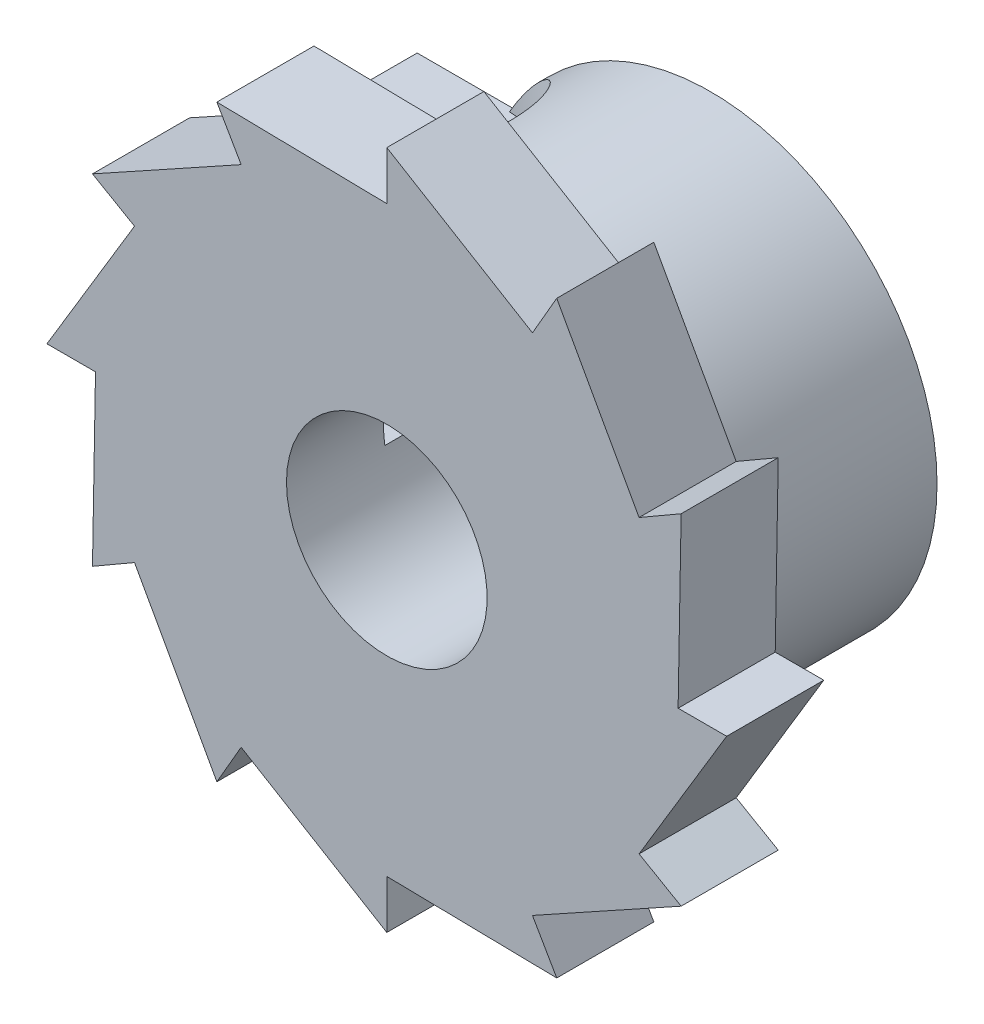
SolidWorks part; units mm, degrees
ref_plane "Front Plane" through (0, 0, 0) normal (0, 0, 1) x (1, 0, 0)
ref_plane "Top Plane" through (0, 0, 0) normal (0, 1, 0) x (1, 0, 0)
ref_plane "Right Plane" through (0, 0, 0) normal (1, 0, 0) x (0, 0, -1)
sketch "Sketch1" plane through (0, 0, 0) normal (0, 0, 1) x (1, 0, 0)
  line L0 (0, 9) -> (0, 10.5)
  line L1 (0.0027, 10.5) -> (-49999.9973, 10.5) construction
  line L2 (0, 0) -> (0, 50000) construction
  line L3 (-0.0178, -0.0309) -> (24999.9822, 43301.2393) construction
  line L4 (0, 9) -> (0, 3.1)
  line L5 (4.5, 7.7942) -> (1.55, 2.6847)
  line L6 (4.5, 7.7942) -> (0, 10.5)
  circle A0 centre (0, 0) radius 9 construction
  circle A1 centre (0, 0) radius 3.1 construction
  arc A2 (0, 10.5) -> (4.5, 7.7942) centre (0, 5.4051) cw construction
  arc A3 (0, 3.1) -> (1.55, 2.6847) centre (0, 0) cw
  dimension "D1" = 6.2
  dimension "D2" = 18
  dimension "D3" = 30
  dimension "D4" = 1.5
extrude "Boss-Extrude1" add sketch "Sketch1" along normal blind 3
pattern_circular "CirPattern1" count 12 over 360 about axis through (0, 0, 3) along (0, 0, -1) of "Boss-Extrude1"
sketch "Sketch3" plane through (0, 0, 0) normal (0, 0, -1) x (-1, 0, 0)
  line L0 (7, -3.5) -> (7, -7)
  line L2 (-7, 0) -> (-7, 7)
  line L3 (-7, 7) -> (9.0622, 7)
  line L5 (7, -7) -> (0, -7)
  line L7 (9.0622, 3.5) -> (9.0622, -3.5)
  line L8 (9.0622, -3.5) -> (7, -3.5)
  line L9 (7, 0) -> (50007, 0) construction
  line L11 (9.0622, 7) -> (9.0622, 3.5)
  line L12 (9, 0) -> (9.0933, -5.25) construction
  arc A0 (7, 0) -> (0, -7) centre (0, 0) ccw construction
  arc A1 (0, -7) -> (-7, 0) centre (0, 0) cw
  circle A2 centre (0, 0) radius 3.1
  circle A3 centre (0, 0) radius 3.1 construction
  point P1 (0, 0)
  point P4 (0, 0)
  point P14 (9.0622, 0)
  point P19 (-5.1866, 6.7966)
  point P20 (0, 0)
  point P21 (7.9021, 7)
  dimension "D1" = 14
  dimension "D3" = 3.5
extrude "Boss-Extrude2" add sketch "Sketch3" along normal blind 7
sketch "Sketch4" plane through (0, 7, 0) normal (0, 1, 0) x (1, 0, 0)
  line L0 (-3.1, 0) -> (3.1, 0) construction
  line L1 (-3.1, 0) -> (3.1, 0) construction
  line L2 (-3.1, 0) -> (-3.1, -50000) construction
  line L4 (-9.0622, 3.75) -> (-3.1, 3.75) construction
  line L5 (-9.0622, 0) -> (-5.9339, 0) construction
  line L6 (-9.0622, 7) -> (-9.0622, 0) construction
  circle A1 centre (-6.0811, 3.75) radius 1.35
  point P9 (-6.0811, 3.75)
  point P11 (-5.6965, 3.75)
  point P12 (0, 0)
  dimension "D1" = 2.7
  dimension "D2" = 3.75
sketch "Sketch6" plane through (-9.0622, 0, 0) normal (-1, 0, 0) x (0, 0, 1)
  line L0 (0, 0) -> (-50000, 0) construction
  line L1 (-7, -0.5) -> (-7, 0.5)
  line L2 (-7, -7) -> (-7, -3.5) construction
  line L3 (-7, 0.5) -> (0, 0.5)
  line L10 (-7, -0.5) -> (0, -0.5)
  line L11 (0, 0) -> (0, 2.3913) construction
  line L12 (0, 0.5) -> (0, -0.5)
  line L13 (-7, -3.5) -> (-7, 7) construction
  point P3 (-7, 0)
  point P12 (-7, 0)
  dimension "D4" = 0.5
sketch "Sketch9" plane through (0, 7, 0) normal (0, 1, 0) x (1, 0, 0)
  circle A0 centre (-6.0811, 3.75) radius 1.75
  point P0 (-6.0811, 3.75)
  point P4 (-5.65, 3.75)
  point P5 (0, 0)
  point P6 (0, 0)
  dimension "D1" = 3.5
extrude "Cut-Extrude19" cut sketch "Sketch6" against normal blind 12.5
extrude "Cut-Extrude20" cut sketch "Sketch9" against normal through all
sketch "Sketch12" plane through (0, 0, -7) normal (0, 0, -1) x (-1, 0, 0)
  line L0 (0, 0) -> (50000, 0) construction
  line L1 (9.0622, -3.5) -> (6.0622, -3.5) construction
  line L2 (0, -7) -> (7, -7) construction
  line L3 (9.0622, 3.5) -> (6.0622, 3.5)
  line L4 (0, -7) -> (7, -7)
  line L5 (7, -7) -> (7, -3.5)
  line L6 (7, -3.5) -> (6.0622, -3.5)
  line L7 (9.0622, 3.5) -> (9.0622, 7)
  line L8 (9.0622, 7) -> (-7, 7)
  line L9 (-7, 7) -> (-7, 0)
  line L10 (9.0622, 7) -> (-7, 7) construction
  arc A0 (0, -7) -> (6.0622, -3.5) centre (0, 0) ccw
  arc A1 (6.0622, 3.5) -> (-7, 0) centre (0, 0) ccw
  point P1 (0, 0)
  point P11 (-7, 7)
  point P27 (0, 0)
  point P28 (0, 0)
  line M9 (9.0622, 0.5) -> (9.0622, 7)
  line M11 (-7, 7) -> (-7, 0)
  line M13 (0, -7) -> (7, -7)
  line M14 (7, -7) -> (7, -3.5)
sketch "Sketch13" plane through (0, 7, 0) normal (0, 1, 0) x (1, 0, 0)
  line L0 (0, 0) -> (0, 50000) construction
  line L2 (0, 0) -> (-9.0622, 0)
  line L3 (0, 0) -> (0, 0.5)
  line L4 (0, 0.5) -> (-9.0622, 0.5)
  line L5 (-9.0622, 0) -> (-9.0622, 0.5)
  line L6 (-9.0622, 7) -> (-9.0622, 0) construction
  point P7 (0, 0)
  point P9 (0, 0)
  dimension "D1" = 0.5
extrude "Cut-Extrude24" cut sketch "Sketch13" against normal up to surface (6.5 mm away) up to face at (-6.0811, 0.5, -2)
sketch "Sketch14" plane through (0, -7, 0) normal (0, -1, 0) x (1, 0, 0)
  circle A0 centre (-6.0811, -3.75) radius 3.1
  point P0 (-6.0811, -3.75)
  dimension "D1" = 6.2
sketch "Sketch15" plane through (0, 7, 0) normal (0, 1, 0) x (1, 0, 0)
  circle A0 centre (-6.0811, 3.75) radius 3.1 construction
  circle A1 centre (-6.0811, 3.75) radius 3.1
extrude "Cut-Extrude29" cut sketch "Sketch12" against normal up to surface (7 mm away) contours A1 L8 M11 | A1 L3 M9 | A0 L6 M13 M14 region at (5.4364, 5.4364, -7) region at (-6.4778, 5.5342, -7) region at (-5.2918, -5.7512, -7) up to face at (-2.8586, 5.3222, 0)
extrude "Cut-Extrude31" cut sketch "Sketch15" against normal up to surface (3.5 mm away) up to face at (-7.357, 3.5, -3.75)
extrude "Cut-Extrude32" cut sketch "Sketch14" against normal up to surface (3.5 mm away) up to face at (-7.357, -3.5, -3.5833)
equation "\"ratchetTeethCount\"= 12"
equation "\"D3@Sketch1\"=360/\"ratchetTeethCount\""
equation "\"D1@CirPattern1\"=\"ratchetTeethCount\""
equation "\"ratchetHeight\"=1.5"
equation "\"D4@Sketch1\"=\"ratchetHeight\""
equation "\"ratchetInnerDiameter\"= 18"
equation "\"D2@Sketch1\"=\"ratchetInnerDiameter\""
